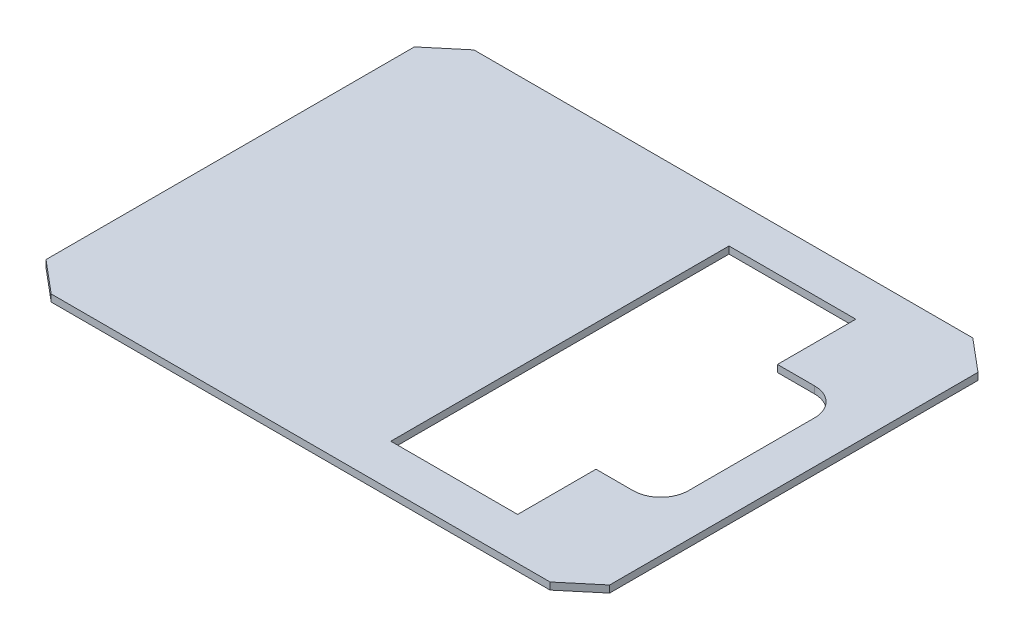
SolidWorks part; units mm, degrees
material "Thornel Mat VMA"
ref_plane "Front Plane" through (0, 0, 0) normal (0, 0, 1) x (1, 0, 0)
ref_plane "Top Plane" through (0, 0, 0) normal (0, 1, 0) x (1, 0, 0)
ref_plane "Right Plane" through (0, 0, 0) normal (1, 0, 0) x (0, 0, -1)
sketch "Sketch1" plane through (0, 0, 0) normal (0, 1, 0) x (1, 0, 0)
  line L0 (0, -95.25) -> (0, 95.25) construction
  line L1 (-127, 95.25) -> (127, 95.25) construction
  line L2 (-127, 95.25) -> (-127, -95.25) construction
  line L3 (-127, -95.25) -> (127, -95.25) construction
  line L4 (127, 95.25) -> (127, -95.25) construction
  line L5 (-127, 0) -> (127, 0) construction
  line L6 (-114.3, 0) -> (-114.3, 52.7344) construction
  line L7 (-114.3, 52.7344) -> (-101.6, 52.7344) construction
  line L8 (-101.6, 52.7344) -> (-87.0069, 64.9795) construction
  line L9 (-87.0069, 64.9795) -> (-87.0069, 76.2) construction
  line L10 (-87.0069, 76.2) -> (0, 76.2) construction
  line L11 (-127, 83.0049) -> (-112.4069, 95.25) construction
  line L12 (-87.0069, 64.9795) -> (-112.4069, 95.25) construction
  line L13 (-101.6, 52.7344) -> (-127, 83.0049) construction
  line L15 (-127, 95.25) -> (127, 95.25) construction
  line L16 (-127, 95.25) -> (-127, -95.25) construction
  line L17 (-127, -95.25) -> (127, -95.25) construction
  line L18 (127, 95.25) -> (127, -95.25) construction
  line L19 (-127, 95.25) -> (127, -95.25) construction
  line L20 (-127, -95.25) -> (127, 95.25) construction
  line L22 (127, -83.0049) -> (112.4069, -95.25)
  line L23 (-127, -83.0049) -> (-112.4069, -95.25)
  line L24 (-112.4069, 95.25) -> (112.4069, 95.25)
  line L25 (-127, -83.0049) -> (-127, 83.0049)
  line L26 (127, 83.0049) -> (127, -83.0049)
  line L27 (112.4069, -95.25) -> (-112.4069, -95.25)
  line L28 (-94.3034, 58.8569) -> (-119.7034, 89.1274) construction
  line L33 (-127, 83.0049) -> (-112.4069, 95.25)
  line L36 (127, 83.0049) -> (112.4069, 95.25)
  point P8 (0, 0)
  point P18 (0, 0)
  dimension "D1" = 190.5
  dimension "D2" = 254
  dimension "D3" = 12.7
  dimension "D4" = 19.05
  dimension "D5" = 12.7
  dimension "D6" = 40
  dimension "D7" = 19.05
  dimension "D8" = 0
  dimension "D9" = 12.7
extrude "Boss-Extrude1" add sketch "Sketch1" along normal blind 3.175 contours L27 L22 L26 L36 L24 L33 L25 L23 region at (0, 0, 0)
sketch "Sketch2" plane through (0, 3.175, 0) normal (0, 1, 0) x (1, 0, 0)
  line L0 (0, 0) -> (127, 0) construction
  line L1 (127, 83.0049) -> (127, -83.0049) construction
  line L2 (78.74, 40.894) -> (107.95, 40.894)
  line L3 (21.59, 76.2) -> (78.74, 76.2)
  line L4 (21.59, 76.2) -> (21.59, -76.2)
  line L5 (21.59, -76.2) -> (78.74, -76.2)
  line L6 (78.74, 76.2) -> (78.74, 40.894)
  line L7 (21.59, 76.2) -> (78.74, -76.2) construction
  line L8 (21.59, -76.2) -> (78.74, 76.2) construction
  line L9 (107.95, 40.894) -> (107.95, -40.894)
  line L10 (127, 83.0049) -> (127, -83.0049) construction
  line L11 (78.74, -40.894) -> (78.74, -76.2)
  line L12 (78.74, -40.894) -> (107.95, -40.894)
  point P5 (50.165, 0)
  point P17 (107.95, 0)
  dimension "D1" = 57.15
  dimension "D2" = 152.4
  dimension "D3" = 48.26
  dimension "D4" = 40.894
  dimension "D5" = 19.05
extrude "Cut-Extrude1" cut sketch "Sketch2" against normal through all
fillet "Fillet1" radius 12.446 2 edges at (107.95, 1.5875, 40.894) (107.95, 1.5875, -40.894)
